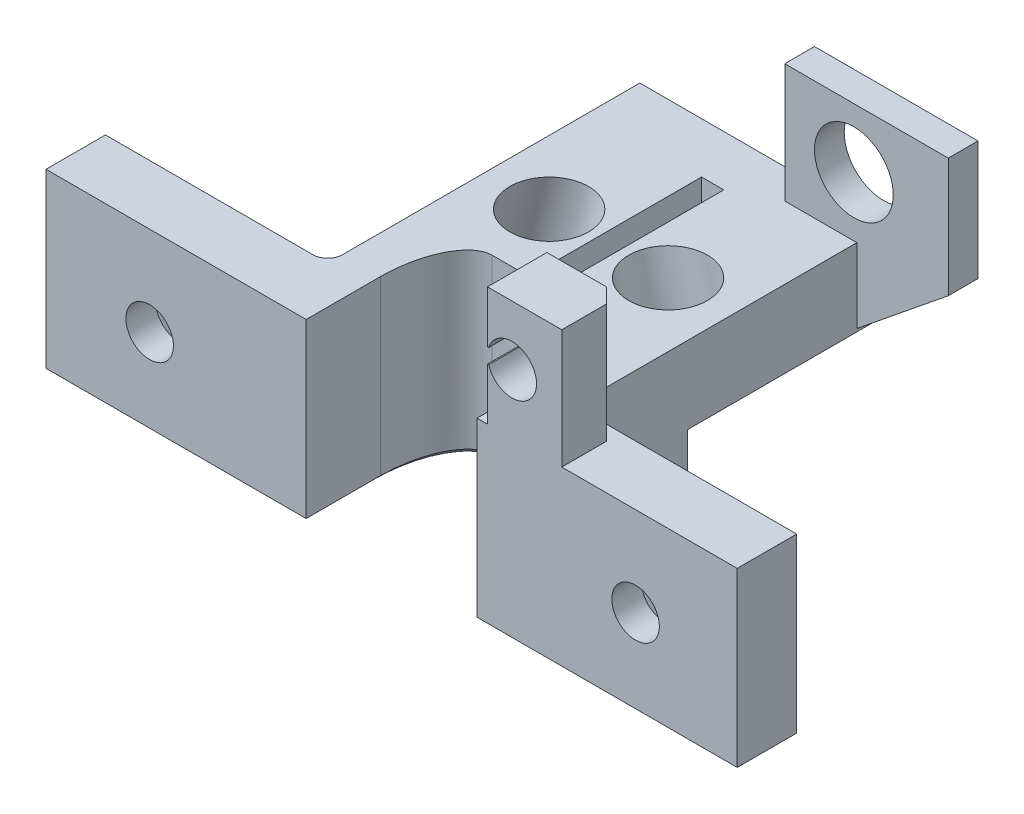
SolidWorks part; units mm, degrees
ref_plane "Front Plane" through (0, 0, 0) normal (0, 0, 1) x (1, 0, 0)
ref_plane "Top Plane" through (0, 0, 0) normal (0, 1, 0) x (1, 0, 0)
ref_plane "Right Plane" through (0, 0, 0) normal (1, 0, 0) x (0, 0, -1)
sketch "Sketch1" plane through (0, 0, 0) normal (0, 1, 0) x (1, 0, 0)
  line L0 (-3.25, -5) -> (-23.25, -5)
  line L1 (-3.25, -5) -> (3.25, -5) construction
  line L2 (-3.25, -5) -> (-3.25, 5) construction
  line L3 (-3.25, 5) -> (3.25, 5)
  line L4 (3.25, -5) -> (3.25, 5) construction
  line L5 (-3.25, -5) -> (3.25, 5) construction
  line L6 (-3.25, 5) -> (3.25, -5) construction
  line L7 (-23.25, -5) -> (-23.25, -1)
  line L8 (-23.25, -1) -> (-9.3, -1)
  line L9 (3.25, -5) -> (23.25, -5)
  line L10 (23.25, -5) -> (23.25, -3)
  line L12 (-8.3, 0) -> (-8.3, 6.6)
  line L13 (-8.3, 6.6) -> (8.3, 6.6)
  line L14 (8.3, 0) -> (8.3, 6.6)
  line L15 (-5.7498, 0) -> (-5.7498, -5)
  line L16 (5.7487, 0) -> (5.7487, -5)
  line L17 (23.25, -3) -> (23.25, -1)
  line L18 (23.25, -1) -> (9.3, -1)
  arc A0 (-9.3, -1) -> (-8.3, 0) centre (-9.3, 0) ccw
  arc A1 (9.3, -1) -> (8.3, 0) centre (9.3, 0) cw
  ellipse E0 centre (-3.25, 0) end of major axis (-3.25, 5) minor radius 2.4998 (-3.25, 5) -> (-3.25, -5) ccw
  ellipse E1 centre (3.25, 0) end of major axis (3.25, 5) minor radius 2.4987 (3.25, -5) -> (3.25, 5) ccw
  point P0 (0, 0)
  dimension "D6" = 1
  dimension "D7" = 4
  dimension "D12" = 1
  dimension "D1" = 6.5
  dimension "D2" = 10
  dimension "D3" = 20
  dimension "D4" = 4
  dimension "D5" = 20
  dimension "D8" = 16.6
  dimension "D9" = 1.6
  dimension "D10" = 5.05
  dimension "D11" = 5.05
extrude "Boss-Extrude1" add sketch "Sketch1" along normal blind 12 contours L8 L7 L0 E0 L3 E1 L9 L10 region at (-14.4999, 0, 4.5207)
sketch "Sketch2" plane through (0, 0, 1) normal (0, 0, -1) x (-1, 0, 0)
  line L0 (-23.3943, 12) -> (-9.4265, 0) construction
  line L1 (-23.25, 0) -> (-9.2822, 12) construction
  line L2 (23.25, 12) -> (9.3079, 0) construction
  line L3 (23.25, 0) -> (9.3, 0) construction
  line L4 (23.25, 0) -> (9.2822, 12) construction
  line L5 (-16.4104, 6) -> (-16.4104, -2.9743) construction
  line L6 (-16.4104, -0.7517) -> (-16.4104, 3) construction
  line L10 (16.2789, 6) -> (16.2789, -2.9743) construction
  line L11 (20.1472, 6) -> (18.2131, 9.35)
  line L12 (-12.5422, 6) -> (-14.4763, 9.35)
  line L13 (-14.4763, 9.35) -> (-18.3445, 9.35)
  line L14 (-18.3445, 9.35) -> (-20.2787, 6)
  line L15 (-20.2787, 6) -> (-18.3445, 2.65)
  line L16 (18.2131, 9.35) -> (14.3448, 9.35)
  line L17 (14.3448, 9.35) -> (12.4107, 6)
  line L18 (-18.3445, 2.65) -> (-14.4763, 2.65)
  line L19 (-14.4763, 2.65) -> (-12.5422, 6)
  line L20 (12.4107, 6) -> (14.3448, 2.65)
  line L21 (14.3448, 2.65) -> (18.2131, 2.65)
  line L22 (18.2131, 2.65) -> (20.1472, 6)
  circle A0 centre (-16.4104, 6) radius 3.35 construction
  circle A1 centre (16.2789, 6) radius 3.35 construction
  point P32 (11.4039, 0.6926)
  dimension "D1" = 6.7
  dimension "D2" = 6.7
extrude "Cut-Extrude1" cut sketch "Sketch2" against normal blind 2
sketch "Sketch3" plane through (0, 12, 0) normal (0, 1, 0) x (1, 0, 0)
  line L0 (-3.25, 5) -> (-3.25, 12.9854) construction
  line L1 (3.25, 5) -> (3.25, 12.9854) construction
  line L2 (-8.3, 6.6) -> (8.3, 6.6)
  line L3 (-8.1382, 9.4853) -> (3.25, 9.4853) construction
  line L4 (-10.9928, 20.2416) -> (10.7178, 20.2416) construction
  line L5 (-8.3, 6.6) -> (-8.3, 20)
  line L6 (-8.3, 20) -> (8.3, 20)
  line L7 (8.3, 20) -> (8.3, 6.6)
  line L8 (-5.7498, -5) -> (-23.25, -5) construction
  circle A1 centre (3.25, 9.4853) radius 2.5 construction
  circle A3 centre (0, 0) radius 13.8 construction
  circle A4 centre (-3.25, 9.4853) radius 2.85 construction
  circle A5 centre (3.25, 9.4853) radius 2.85 construction
  circle A7 centre (0, 0) radius 13 construction
  line M20 (8.3, 6.6) -> (-8.3, 6.6)
  dimension "D1" = 20.2416
  dimension "D2" = 25
  dimension "D3" = 27.6
  dimension "D4" = 5.7
  dimension "D5" = 5.7
  dimension "D9" = 26
extrude "Boss-Extrude2" add sketch "Sketch3" against normal blind 5.2 contours M20 region at (0, 12, -13.3)
sketch "Sketch4" [suppressed] plane through (0, 6.8, 0) normal (0, -1, 0) x (1, 0, 0)
  line L0 (-8.3, -6.6) -> (8.3, -6.6)
  line L1 (8.3, -6.6) -> (8.3, -11.9594)
  line L2 (-8.3, -6.6) -> (-8.3, -9.2406)
  ellipse E1 centre (0, -10.6) end of major axis (8.3, -12.6) minor radius 3.3362 (-8.3, -9.2406) -> (8.3, -11.9594) ccw
extrude "Boss-Extrude3" [suppressed] add sketch "Sketch4" along normal blind 5
chamfer "Chamfer1" [suppressed] distance 0.5 angle 45
sketch "Sketch5" plane through (0, 0, 1) normal (0, 0, -1) x (-1, 0, 0)
  line L0 (12.4107, 6) -> (20.1472, 6) construction
  line L1 (20.1472, 6) -> (18.2131, 9.35) construction
  line L2 (20.1472, 6) -> (18.2131, 9.35) construction
  line L3 (16.2789, 9.35) -> (16.2789, 2.65) construction
  line L4 (18.2131, 9.35) -> (14.3448, 9.35) construction
  line L5 (14.3448, 2.65) -> (18.2131, 2.65) construction
  line L6 (-16.4104, 9.35) -> (-16.4104, 2.65) construction
  line L7 (-14.4763, 9.35) -> (-18.3445, 9.35) construction
  line L8 (-18.3445, 2.65) -> (-14.4763, 2.65) construction
  line L9 (-20.2787, 6) -> (-12.5422, 6) construction
  circle A0 centre (-16.4104, 6) radius 1.6
  circle A1 centre (16.2789, 6) radius 1.6
  dimension "D1" = 3.2
  dimension "D2" = 3.2
extrude "Cut-Extrude2" cut sketch "Sketch5" against normal blind 5
sketch "Sketch6" plane through (0, 12, 0) normal (0, 1, 0) x (1, 0, 0)
  line L0 (5.7487, -5) -> (23.25, -5) construction
  line L1 (6.4487, -5) -> (11.4487, -5)
  line L2 (6.4487, -5) -> (6.4487, -1)
  line L3 (6.4487, -1) -> (11.4487, -1)
  line L4 (11.4487, -5) -> (11.4487, -1)
  line L6 (5.7487, 0) -> (5.7487, -5) construction
  dimension "D1" = 4
  dimension "D2" = 0.7
  dimension "D3" = 5
extrude "Boss-Extrude4" add sketch "Sketch6" along normal blind 8
sketch "Sketch7" plane through (0, 0, 1) normal (0, 0, -1) x (-1, 0, 0)
  line L1 (-6.4487, 12) -> (-6.4487, 20) construction
  line L2 (-6.4487, 16) -> (-15.0595, 16) construction
  line L4 (-5.584, 16.5) -> (-7.9994, 16.5)
  line L5 (-5.584, 16.5) -> (-5.584, 15.5)
  line L6 (-5.584, 15.5) -> (-7.9994, 15.5)
  line L7 (-7.9994, 16.5) -> (-7.9994, 15.5)
  line L8 (-5.584, 16.5) -> (-7.9994, 15.5) construction
  line L9 (-5.584, 15.5) -> (-7.9994, 16.5) construction
  circle A0 centre (-8.0987, 16) radius 1.65
  point P6 (-6.7917, 16)
  line M11 (-6.4487, 12) -> (-6.4487, 20)
  dimension "D1" = 3.3
  dimension "D2" = 1
extrude "Cut-Extrude4" cut sketch "Sketch7" against normal blind 7 contours L4 A0 L6 L7 | A0 L4 L7 L6 | A0 L6 M11 | A0 L4 M11 region at (6.4719, 16.3756, 1) region at (7.2367, 16, 1) region at (8.2858, 16, 1) region at (6.4719, 15.6244, 1)
sketch "Sketch8" plane through (0, 12, 0) normal (0, 1, 0) x (1, 0, 0)
  line L0 (8.3, 12.6) -> (-8.3, 12.6) construction
  line L1 (0, 12.6) -> (0, 3.5286) construction
  line L2 (-9.6265, 9.6) -> (9.6265, 9.6) construction
  line L4 (-3.25, 5) -> (3.25, 5) construction
  circle A0 centre (-4, 9.6) radius 2.65
  point P10 (0, 9.6)
  dimension "D2" = 5.3
  dimension "D3" = 7.6
  dimension "D1" = 3
  dimension "D4" = 4
sketch3d "3DSketch1"
  line L0 (0, 24, -5) -> (8.119, -6.3005, -5) construction
  line L1 (-3.25, 12, -5) -> (3.25, 12, -5) construction
  line L2 (3.25, 12, -5) -> (-3.25, 12, -5) construction
  line L3 (0, 12, -5) -> (0, -3.1746, -5) construction
  line L4 (0, 12, -5) -> (0, 24, -5) construction
  line L5 (0, 24, -5) -> (-8.2564, -6.8133, -5) construction
  point P7 (0, 12, -5)
  dimension "D1" = 12
  dimension "D2" = 15
  dimension "D3" = 15
extrude "Cut-Extrude5" cut sketch "Sketch8" along direction (-0.2588, -0.9659, 0) on the side against the normal blind 7
ref_plane "Plane1" through (8.119, -6.3005, -5) normal (0.2588, -0.9659, 0) x (-0.9659, -0.2588, 0)
sketch "Sketch10" plane through (0, 12, 0) normal (0, 1, 0) x (1, 0, 0)
  line L0 (-8.3, 12.6) -> (8.3, 12.6) construction
  line L1 (0, 12.6) -> (0, 2.6194) construction
  line L2 (-11.9688, 9.6) -> (11.9688, 9.6) construction
  line L3 (0, 5) -> (8.119, 5) construction
  circle A0 centre (4, 9.6) radius 2.65
  point P10 (0, 9.6)
  dimension "D3" = 5.3
  dimension "D1" = 3
  dimension "D2" = 4
  dimension "D4" = 7.6
extrude "Cut-Extrude6" cut sketch "Sketch10" along direction (0.2588, -0.9659, 0) on the side against the normal blind 7
chamfer "Chamfer2" distance 2 angle 45 1 edges at (7.8743, 12, 1)
chamfer "Chamfer3" distance 1 angle 45 1 edges at (11.4487, 16, 1)
sketch "Sketch12" plane through (0, 12, 0) normal (0, 1, 0) x (1, 0, 0)
  line L0 (5.7487, 0) -> (5.7487, 22.8142) construction
  line L1 (6.4487, 1) -> (6.4487, 22.8142) construction
  line L2 (11.4487, -5) -> (23.25, -5) construction
  line L3 (6.4487, 20) -> (14.4487, 20)
  line L4 (6.4487, 20) -> (6.4487, 18)
  line L5 (6.4487, 18) -> (14.4487, 18)
  line L6 (14.4487, 20) -> (14.4487, 18)
  line L8 (6.4487, 20) -> (3.4487, 20)
  line L9 (6.4487, 20) -> (6.4487, 18)
  line L10 (6.4487, 18) -> (3.4487, 18)
  line L11 (3.4487, 20) -> (3.4487, 18)
  line M8 (8.3, 1) -> (8.3, 20)
  dimension "D1" = 8
  dimension "D2" = 2
  dimension "D3" = 23
  dimension "D4" = 3
extrude "Boss-Extrude5" add sketch "Sketch12" along normal blind 8 contours L8 L11 L10 L4 | L6 L3 L5 M8 | L4 L5 L3 M8 region at (7.3743, 12, -19) region at (4.9487, 12, -19) region at (11.3743, 12, -19)
sketch "Sketch13" plane through (0, 0, -20) normal (0, 0, -1) x (-1, 0, 0)
  line L0 (-6.4487, 20) -> (-6.4487, 12) construction
  line L1 (8.3, 12) -> (-3.4487, 12) construction
  line L3 (-6.4487, 16) -> (-16.867, 16) construction
  circle A0 centre (-8.0987, 16) radius 1.65 construction
  circle A1 centre (-8.0987, 16) radius 2.65
  dimension "D1" = 3.3
  dimension "D2" = 5.3
  dimension "D3" = 1.8513
extrude "Cut-Extrude7" cut sketch "Sketch13" against normal blind 3
chamfer "Chamfer4" distance 5 angle 51 1 edges at (8.3, 12, -19) first distance on face at (8.3, 7.825, -9.025)
sketch "Sketch16" plane through (0, 6.8, 0) normal (0, -1, 0) x (1, 0, 0)
  line L0 (-8.3, -6.6) -> (8.3, -6.6) construction
  line L1 (0, -6.6) -> (0, -20) construction
  line L2 (-8.3, -20) -> (8.3, -20) construction
  line L4 (-0.75, -16.6) -> (0.75, -16.6)
  line L5 (-0.75, -16.6) -> (-0.75, -6.6)
  line L6 (-0.75, -6.6) -> (0.75, -6.6)
  line L7 (0.75, -16.6) -> (0.75, -6.6)
  line L8 (-0.75, -16.6) -> (0.75, -6.6) construction
  line L9 (-0.75, -6.6) -> (0.75, -16.6) construction
  point P8 (0, -11.6)
  dimension "D1" = 1.5
  dimension "D2" = 10
extrude "Cut-Extrude8" cut sketch "Sketch16" against normal blind 11
chamfer "Chamfer5" distance 0.4 angle 45 16 edges at (5.7487, 0, 2.5) (14.4993, 0, 5) (23.25, 0, 3) (16.275, 0, 1) (8.5929, 0, 0.7071) (8.3, 0, -3.3) (0, 0, -6.6) (-8.3, 0, -3.3) (-8.5929, 0, 0.7071) (-16.275, 0, 1) (-23.25, 0, 3) (-14.4999, 0, 5) (-5.7498, 0, 2.5) (-5.0176, 0, -3.5355) (0, 0, -5) (5.0168, 0, -3.5355)
